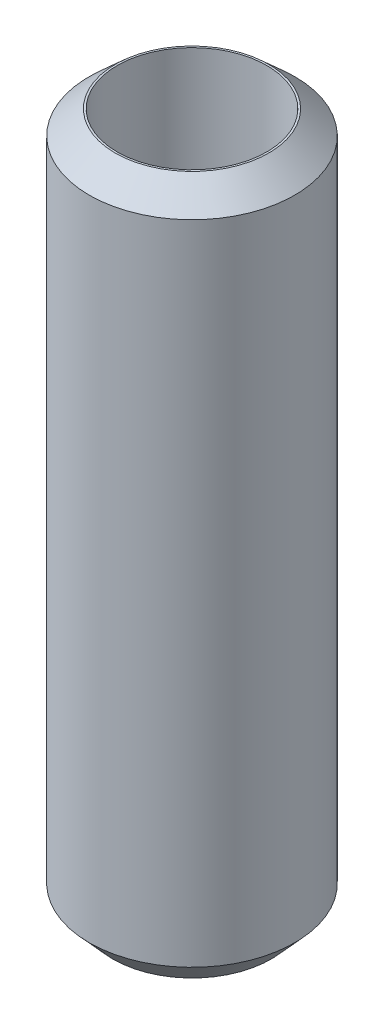
SolidWorks part; units mm, degrees
ref_plane "Front Plane" through (0, 0, 0) normal (0, 0, 1) x (1, 0, 0)
ref_plane "Top Plane" through (0, 0, 0) normal (0, 1, 0) x (1, 0, 0)
ref_plane "Right Plane" through (0, 0, 0) normal (1, 0, 0) x (0, 0, -1)
sketch "Sketch1" plane through (0, 0, 0) normal (0, 1, 0) x (1, 0, 0)
  circle A0 centre (0, 0) radius 25
  dimension "SHAFT_OD" = 50
extrude "Boss-Extrude1" add sketch "Sketch1" along normal blind 169.5471
sketch "Sketch2" plane through (0, 0, 0) normal (0, 1, 0) x (1, 0, 0)
  circle A0 centre (0, 0) radius 18.2172
  dimension "BORE_D" = 36.4345
extrude "Cut-Extrude1" cut sketch "Sketch2" along normal through all
chamfer "Chamfer1" distance 5.7222 angle 47.798 2 edges at (0, 169.5471, 25) (0, 0, 25) first distance on face at (0, 169.5471, 25) first distance on face at (0, 0, 18.2172)
